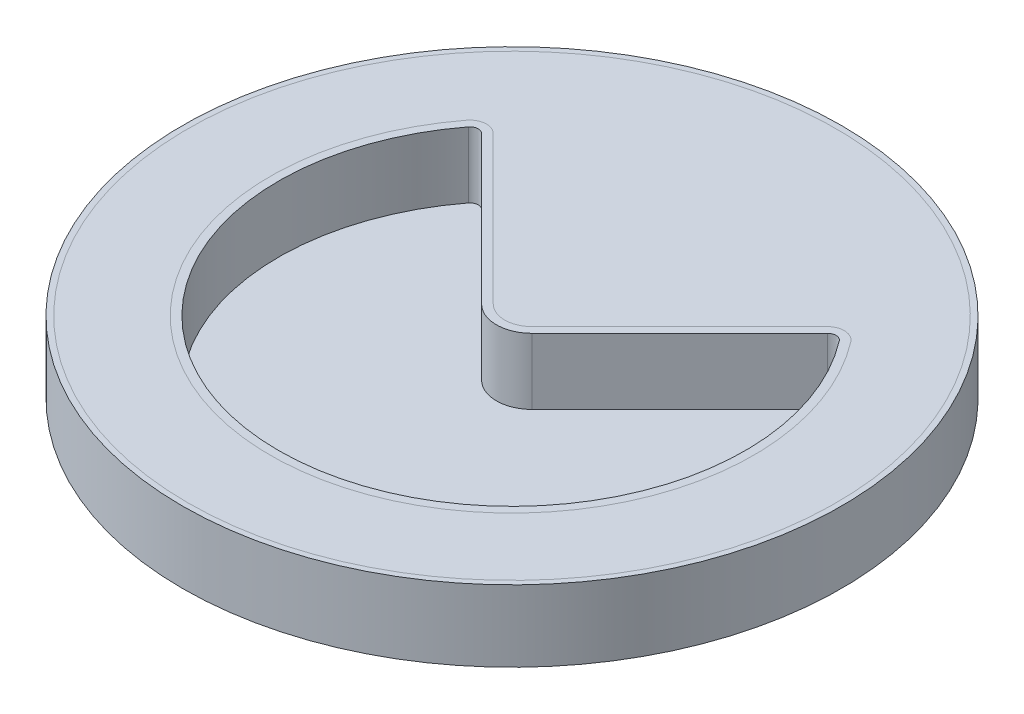
SolidWorks part; units mm, degrees
ref_plane "Front" through (0, 0, 0) normal (0, 0, 1) x (1, 0, 0)
ref_plane "Top" through (0, 0, 0) normal (0, 1, 0) x (1, 0, 0)
ref_plane "Right" through (0, 0, 0) normal (1, 0, 0) x (0, 0, -1)
sketch "Sketch1" plane through (0, 0, 0) normal (0, 1, 0) x (1, 0, 0)
  line L0 (0, 69.6036) -> (0, -75.338) construction
  line L1 (-29.7375, 27.7375) -> (-2.8284, 0.8284)
  line L2 (2.8284, 0.8284) -> (29.7375, 27.7375)
  circle A0 centre (0, 0) radius 60
  arc A1 (-35.7431, 27.3392) -> (35.7431, 27.3392) centre (0, 0) ccw
  arc A2 (29.7375, 27.7375) -> (35.7431, 27.3392) centre (32.5659, 24.9091) cw
  arc A3 (-2.8284, 0.8284) -> (2.8284, 0.8284) centre (0, 3.6569) ccw
  arc A4 (-29.7375, 27.7375) -> (-35.7431, 27.3392) centre (-32.5659, 24.9091) ccw
  point P14 (0, -2)
  dimension "D1" = 120
  dimension "D2" = 45
  dimension "D5" = 4
  dimension "D3" = 2
  dimension "D4" = 90
extrude "Extrude-Thin1" add sketch "Sketch1" along normal blind 12 thin thin type one direction reverse wall 2.5
sketch "Sketch2" plane through (0, 0, 0) normal (0, 1, 0) x (1, 0, 0)
  circle A0 centre (0, 0) radius 60
extrude "Boss-Extrude1" add sketch "Sketch2" against normal blind 1
sketch "Sketch5" plane through (0, 12, 0) normal (0, 1, 0) x (1, 0, 0)
  line L4 (30.4446, 27.0304) -> (3.5355, 0.1213)
  line L5 (-3.5355, 0.1213) -> (-30.4446, 27.0304)
  line L6 (30.4446, 27.0304) -> (3.5355, 0.1213)
  line L7 (-3.5355, 0.1213) -> (-30.4446, 27.0304)
  circle A6 centre (0, 0) radius 59
  circle A7 centre (0, 0) radius 59
  arc A8 (-30.4446, 27.0304) -> (-34.9488, 26.7317) centre (-32.5659, 24.9091) ccw
  arc A9 (-34.9488, 26.7317) -> (34.9488, 26.7317) centre (0, 0) ccw
  arc A10 (34.9488, 26.7317) -> (30.4446, 27.0304) centre (32.5659, 24.9091) ccw
  arc A11 (-3.5355, 0.1213) -> (3.5355, 0.1213) centre (0, 3.6569) ccw
  arc A12 (-30.4446, 27.0304) -> (-34.9488, 26.7317) centre (-32.5659, 24.9091) ccw
  arc A13 (-34.9488, 26.7317) -> (34.9488, 26.7317) centre (0, 0) ccw
  arc A14 (34.9488, 26.7317) -> (30.4446, 27.0304) centre (32.5659, 24.9091) ccw
  arc A15 (-3.5355, 0.1213) -> (3.5355, 0.1213) centre (0, 3.6569) ccw
  dimension "D1" = 1
  dimension "D2" = 1
extrude "Cut-Extrude1" cut sketch "Sketch5" against normal blind 1
sketch "Sketch4" plane through (0, 12, 0) normal (0, 1, 0) x (1, 0, 0)
  line L0 (30.4446, 27.0304) -> (3.5355, 0.1213) construction
  line L1 (-3.5355, 0.1213) -> (-30.4446, 27.0304) construction
  line L4 (-4.5962, -0.9393) -> (-31.5053, 25.9697) construction
  line L5 (31.5053, 25.9697) -> (4.5962, -0.9393) construction
  line L6 (-4.5962, -0.9393) -> (-31.5053, 25.9697)
  line L7 (31.5053, 25.9697) -> (4.5962, -0.9393)
  line L8 (30.4446, 27.0304) -> (3.5355, 0.1213)
  line L9 (-3.5355, 0.1213) -> (-30.4446, 27.0304)
  arc A1 (-30.4446, 27.0304) -> (-34.9488, 26.7317) centre (-32.5659, 24.9091) ccw construction
  arc A4 (-31.5053, 25.9697) -> (-33.7573, 25.8204) centre (-32.5659, 24.9091) ccw construction
  arc A6 (33.7573, 25.8204) -> (31.5053, 25.9697) centre (32.5659, 24.9091) ccw construction
  arc A7 (-4.5962, -0.9393) -> (4.5962, -0.9393) centre (0, 3.6569) ccw construction
  arc A8 (-31.5053, 25.9697) -> (-33.7573, 25.8204) centre (-32.5659, 24.9091) ccw
  arc A10 (33.7573, 25.8204) -> (31.5053, 25.9697) centre (32.5659, 24.9091) ccw
  arc A11 (-4.5962, -0.9393) -> (4.5962, -0.9393) centre (0, 3.6569) ccw
  arc A12 (-34.9488, 26.7317) -> (34.9488, 26.7317) centre (0, 0) ccw construction
  arc A13 (34.9488, 26.7317) -> (30.4446, 27.0304) centre (32.5659, 24.9091) ccw construction
  arc A14 (-3.5355, 0.1213) -> (3.5355, 0.1213) centre (0, 3.6569) ccw construction
  arc A15 (-30.4446, 27.0304) -> (-34.9488, 26.7317) centre (-32.5659, 24.9091) ccw
  arc A16 (-34.9488, 26.7317) -> (34.9488, 26.7317) centre (0, 0) ccw
  arc A17 (34.9488, 26.7317) -> (30.4446, 27.0304) centre (32.5659, 24.9091) ccw
  arc A18 (-3.5355, 0.1213) -> (3.5355, 0.1213) centre (0, 3.6569) ccw
  circle A19 centre (0, 0) radius 59 construction
  circle A20 centre (0, 0) radius 59
  circle M13 centre (0, 0) radius 59
extrude "Boss-Extrude3" add sketch "Sketch4" against normal blind 1 separate body contours L9 A18 L8 A17 A16 A15 M13 region at (0, 12, -6.5861)
